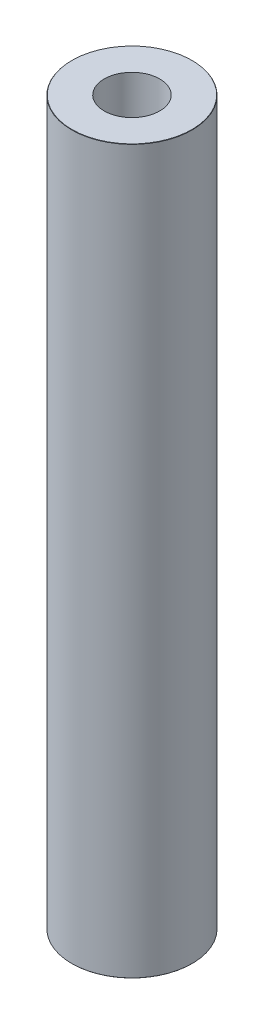
SolidWorks part; units mm, degrees
ref_plane "Front Plane" through (0, 0, 0) normal (0, 0, 1) x (1, 0, 0)
ref_plane "Top Plane" through (0, 0, 0) normal (0, 1, 0) x (1, 0, 0)
ref_plane "Right Plane" through (0, 0, 0) normal (1, 0, 0) x (0, 0, -1)
sketch "Sketch1" plane through (0, 0, 0) normal (0, 1, 0) x (1, 0, 0)
  circle A0 centre (0, 0) radius 50
  dimension "SHAFT_OD" = 100
extrude "Boss-Extrude1" add sketch "Sketch1" along normal blind 600
sketch "Sketch2" plane through (0, 0, 0) normal (0, 1, 0) x (1, 0, 0)
  circle A0 centre (0, 0) radius 23.0674
  dimension "BORE_D" = 46.1347
extrude "Cut-Extrude1" cut sketch "Sketch2" along normal through all
chamfer "Chamfer1" distance 0.2024 angle 45 2 edges at (0, 600, 50) (0, 0, 50)
